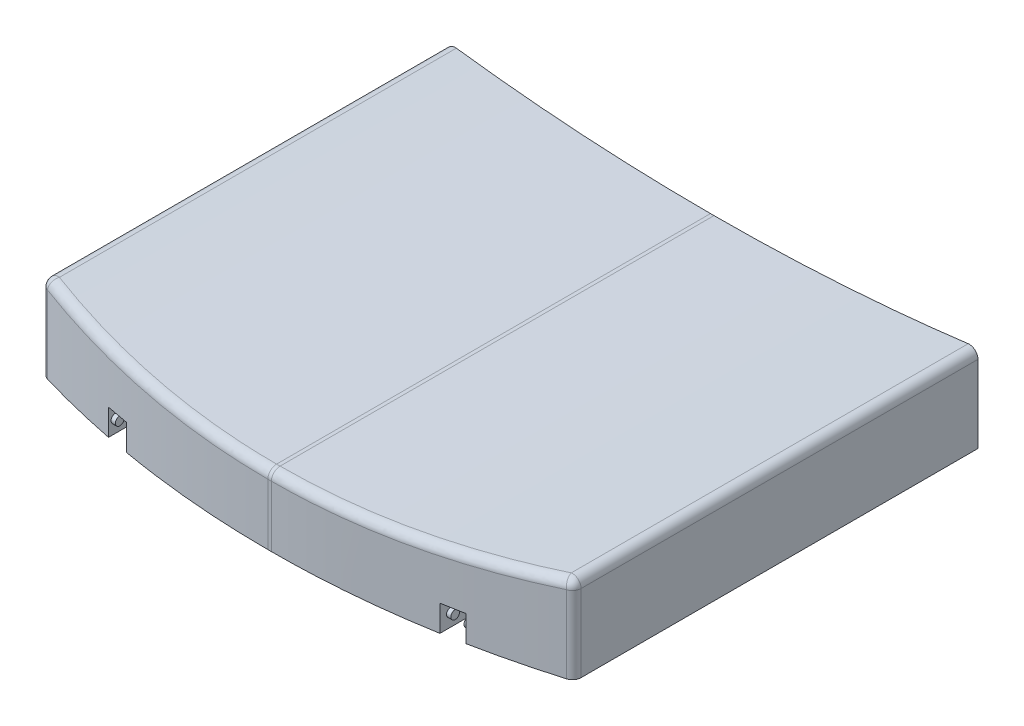
SolidWorks part; units mm, degrees
ref_plane "Front Plane" through (0, 0, 0) normal (0, 0, 1) x (1, 0, 0)
ref_plane "Top Plane" through (0, 0, 0) normal (0, 1, 0) x (1, 0, 0)
ref_plane "Right Plane" through (0, 0, 0) normal (1, 0, 0) x (0, 0, -1)
sketch "Sketch1" plane through (0, 0, 0) normal (0, 1, 0) x (1, 0, 0)
  line L1 (-305, 254) -> (305, 254)
  line L2 (-305, 254) -> (-305, -254)
  line L3 (-305, -254) -> (305, -254)
  line L4 (305, 254) -> (305, -254)
  line L5 (-305, 254) -> (305, -254) construction
  line L6 (-305, -254) -> (305, 254) construction
  point P0 (0, 0)
  dimension "D1" = 610
  dimension "D2" = 508
extrude "Boss-Extrude1" add sketch "Sketch1" along normal blind 100
sketch "Sketch2" plane through (0, 0, 0) normal (0, 0, 1) x (1, 0, 0)
  line L0 (0, 100) -> (0, 80) construction
  line L1 (0, -55) -> (0, 55) construction
  line L2 (-305, 100) -> (305, 100) construction
  line L3 (0, 80) -> (2, 80)
  line L4 (0, 80) -> (-2, 80)
  line L5 (-305, 100) -> (305, 100)
  spline S0 degree 2 poles (305, 100) (153.8297, 80) (2, 80) knots 0 0 0 1 1 1
  spline S1 degree 2 poles (-2, 80) (-153.8297, 80) (-305, 100) knots 0 0 0 1 1 1
  dimension "D1" = 2
  dimension "D2" = 20
extrude "Cut-Extrude1" cut sketch "Sketch2" against normal mid plane 508
sketch "Sketch5" plane through (0, 0, 0) normal (0, 1, 0) x (1, 0, 0)
  line L0 (-2, -254) -> (0, -254)
  line L1 (-305, -254) -> (-2, -254) construction
  line L2 (0, -55) -> (0, 55) construction
  line L3 (0, -254) -> (2, -254)
  line L4 (2, -254) -> (305, -254) construction
  line L5 (-305, -254) -> (-305, -209)
  line L6 (-305, 254) -> (-305, -254) construction
  line L7 (305, -254) -> (305, -209)
  line L8 (305, -254) -> (305, 254) construction
  line L10 (-305, -254) -> (-305, -264)
  line L11 (305, -254) -> (305, -264)
  line L12 (-305, -264) -> (305, -264)
  spline S0 degree 2 poles (-305, -209) (-154.5074, -254) (-2, -254) knots 0 0 0 1 1 1
  spline S1 degree 2 poles (2, -254) (154.5074, -254) (305, -209) knots 0 0 0 1 1 1
  dimension "D1" = 2
  dimension "D2" = 45
  dimension "D3" = 45
  dimension "D4" = 10
extrude "Cut-Extrude2" cut sketch "Sketch5" along normal blind 100
fillet "Fillet1" radius 10 7 edges at (157.343, 85.2457, 242.2486) (0, 80, 254) (305, 50, 209) (-305, 50, 209) (305, 100, -22.5) (-78.2438, 81.2622, 251.1789) (-305, 100, -22.5)
sketch "Sketch6" plane through (0, 0, 0) normal (0, 1, 0) x (1, 0, 0)
  line L0 (-305, 254) -> (-305, -201.5268) construction
  line L1 (-205, -241) -> (-180, -241)
  line L2 (-205, -241) -> (-205, -206)
  line L3 (-205, -206) -> (-180, -206)
  line L4 (-180, -241) -> (-180, -206)
  line L5 (-205, -241) -> (-180, -206) construction
  line L6 (-205, -206) -> (-180, -241) construction
  line L7 (305, 254) -> (-305, 254) construction
  point P0 (-192.5, -223.5)
  dimension "D1" = 25
  dimension "D2" = 35
  dimension "D3" = 100
  dimension "D4" = 460
extrude "Cut-Extrude3" cut sketch "Sketch6" along normal blind 30
sketch "Sketch7" plane through (-180, 0, 0) normal (-1, 0, 0) x (0, 0, 1)
  line L0 (226, 30) -> (226, 2.5798) construction
  line L2 (238.5553, 15) -> (217.2652, 15) construction
  line L3 (238.5553, 30) -> (238.5553, 0) construction
  line L4 (206, 30) -> (206, 0) construction
  circle A0 centre (226, 15) radius 5
  dimension "D1" = 10
  dimension "D2" = 20
extrude "Boss-Extrude2" add sketch "Sketch7" along normal blind 5
sketch "Sketch8" plane through (-205, 0, 0) normal (1, 0, 0) x (0, 0, -1)
  line L0 (-226, 30) -> (-226, 12.7746) construction
  line L2 (-206, 15) -> (-237.3973, 15) construction
  line L3 (-206, 30) -> (-206, 0) construction
  circle A0 centre (-226, 15) radius 5
  dimension "D1" = 10
  dimension "D2" = 20
extrude "Boss-Extrude3" add sketch "Sketch8" along normal blind 5
mirror "Mirror1" about plane through (0, 0, 0) normal (1, 0, 0) of "Boss-Extrude3", "Cut-Extrude3", "Boss-Extrude2"
